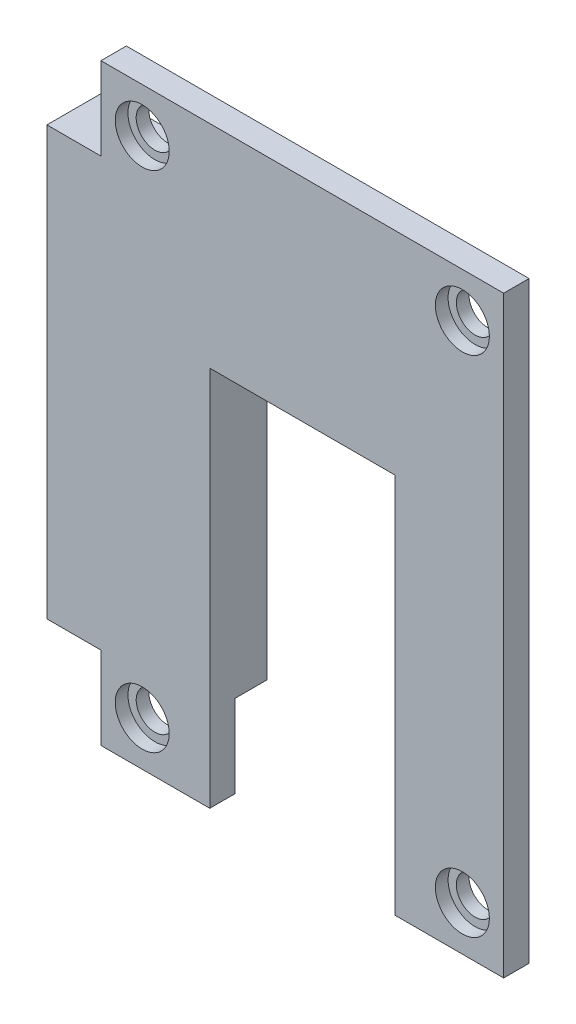
SolidWorks part; units mm, degrees
ref_plane "Alzado" through (0, 0, 0) normal (0, 0, 1) x (1, 0, 0)
ref_plane "Planta" through (0, 0, 0) normal (0, 1, 0) x (1, 0, 0)
ref_plane "Vista lateral" through (0, 0, 0) normal (1, 0, 0) x (0, 0, -1)
sketch "Croquis1" plane through (0, 0, 0) normal (0, 0, 1) x (1, 0, 0)
  line L0 (0, 93.345) -> (64.3868, 93.345)
  line L1 (0, 93.345) -> (0, 0)
  line L2 (0, 0) -> (64.3868, 0)
  line L3 (64.3868, 93.345) -> (64.3868, 0)
  dimension "D1" = 64.3868
  dimension "D2" = 93.345
extrude "Saliente-Extruir1" add sketch "Croquis1" along normal blind 4
sketch "Croquis2" plane through (0, 0, 4) normal (0, 0, 1) x (1, 0, 0)
  line L5 (0, 0) -> (64.3868, 0) construction
  line L6 (18.63, 0) -> (45.7568, 0)
  line L7 (18.63, 0) -> (18.63, 60)
  line L8 (18.63, 60) -> (45.7568, 60)
  line L9 (45.7568, 0) -> (45.7568, 60)
  line L10 (64.3868, 0) -> (64.3868, 93.345) construction
  line L11 (0, 93.345) -> (0, 0) construction
  dimension "D1" = 18.63
  dimension "D2" = 18.63
  dimension "D3" = 60
extrude "Cortar-Extruir1" cut sketch "Croquis2" against normal through all
sketch "Croquis5" plane through (0, 0, 4) normal (0, 0, 1) x (1, 0, 0)
  line L0 (64.3868, 0) -> (64.3868, 93.345) construction
  line L1 (64.3868, 93.345) -> (0, 93.345) construction
  line L2 (0, 93.345) -> (0, 0) construction
  line L3 (45.7568, 0) -> (64.3868, 0) construction
  circle A0 centre (57.3868, 86.345) radius 4.25
  circle A1 centre (7, 86.345) radius 4.25
  circle A2 centre (57.3868, 7) radius 4.25
  circle A3 centre (7, 7) radius 4.25
  dimension "D5" = 8.5
  dimension "D1" = 7
  dimension "D2" = 7
  dimension "D3" = 7
  dimension "D4" = 7
  dimension "D6" = 7
extrude "Cortar-Extruir3" cut sketch "Croquis5" against normal blind 2
sketch "Croquis6" plane through (0, 0, 2) normal (0, 0, 1) x (1, 0, 0)
  circle A0 centre (7, 86.345) radius 2.95
  circle A1 centre (57.3868, 86.345) radius 2.95
  circle A2 centre (57.3868, 7) radius 2.95
  circle A3 centre (7, 7) radius 2.95
  dimension "D1" = 5.9
extrude "Cortar-Extruir4" cut sketch "Croquis6" against normal through all
sketch "Croquis7" plane through (0, 0, 0) normal (0, 0, -1) x (-1, 0, 0)
  line L0 (0, 13) -> (0, 80.345)
  line L3 (0, 13) -> (8, 13)
  line L4 (8, 80.345) -> (8, 13)
  line L5 (0, 93.345) -> (0, 0) construction
  line L6 (0, 80.345) -> (8, 80.345)
  line L7 (-64.3868, 93.345) -> (0, 93.345) construction
  dimension "D1" = 8
  dimension "D2" = 13
  dimension "D3" = 13
extrude "Saliente-Extruir4" add sketch "Croquis7" against normal through all
sketch "Croquis8" plane through (0, 0, 0) normal (0, 0, -1) x (-1, 0, 0)
  line L0 (-18.63, 60) -> (-18.63, 0) construction
  line L1 (8, 80.345) -> (-18.63, 80.345)
  line L2 (8, 80.345) -> (8, 13)
  line L3 (8, 13) -> (-18.63, 13)
  line L4 (-18.63, 80.345) -> (-18.63, 13)
extrude "Saliente-Extruir5" add sketch "Croquis8" along normal blind 5
sketch "Croquis9" plane through (0, 0, 0) normal (0, 0, -1) x (-1, 0, 0)
  line L0 (-64.3868, 93.345) -> (0, 93.345) construction
  line L1 (-63.8868, 93.345) -> (-0.5, 93.345) construction
  line L2 (-63.8868, 93.345) -> (-63.8868, 0)
  line L3 (-63.8868, 0) -> (-0.5, 0) construction
  line L4 (-0.5, 93.345) -> (-0.5, 0) construction
  line L5 (0, 0) -> (-18.63, 0) construction
  line L6 (0, 93.345) -> (0, 80.345) construction
  line L7 (-64.3868, 0) -> (-64.3868, 93.345) construction
  line L8 (-0.5, 93.345) -> (0, 93.345)
  line L9 (0, 93.345) -> (0, 80.345)
  line L10 (0, 80.345) -> (-0.5, 80.345)
  line L11 (-0.5, 0) -> (0, 0)
  line L12 (0, 0) -> (0, 13)
  line L13 (0, 13) -> (-0.5, 13)
  line L14 (-18.63, 13) -> (0, 13) construction
  line L15 (-63.8868, 93.345) -> (-64.3868, 93.345)
  line L16 (-64.3868, 93.345) -> (-64.3868, 0)
  line L17 (-64.3868, 0) -> (-63.8868, 0)
  line L18 (-0.5, 13) -> (-0.5, 0)
  line L19 (-0.5, 80.345) -> (-0.5, 93.345)
  dimension "D1" = 0.5
  dimension "D2" = 0.5
extrude "Cortar-Extruir5" cut sketch "Croquis9" against normal blind 13
sketch "Croquis10" plane through (0, 0, -5) normal (0, 0, -1) x (-1, 0, 0)
  line L0 (8, 13) -> (8, 80.345) construction
  line L1 (8, 56.345) -> (3, 56.345)
  line L2 (8, 56.345) -> (8, 36.345)
  line L3 (8, 36.345) -> (3, 36.345)
  line L4 (3, 56.345) -> (3, 36.345)
  dimension "D1" = 20
  dimension "D2" = 24
  dimension "D3" = 5
extrude "Saliente-Extruir6" add sketch "Croquis10" along normal blind 23
sketch "Croquis11" plane through (0, 0, -28) normal (0, 0, -1) x (-1, 0, 0)
  line L0 (3, 36.345) -> (8, 36.345) construction
  line L1 (8, 56.345) -> (-12, 56.345)
  line L2 (8, 56.345) -> (8, 36.345)
  line L3 (8, 36.345) -> (-12, 36.345)
  line L4 (-12, 56.345) -> (-12, 36.345)
  dimension "D1" = 20
extrude "Saliente-Extruir7" add sketch "Croquis11" along normal blind 5
sketch "Croquis12" plane through (0, 0, -5) normal (0, 0, -1) x (-1, 0, 0)
  line L0 (-45.7568, 0) -> (-63.8868, 0) construction
  line L1 (-17.63, 60) -> (-46.7568, 60)
  line L2 (-17.63, 60) -> (-17.63, 0)
  line L3 (-17.63, 0) -> (-46.7568, 0)
  line L4 (-46.7568, 60) -> (-46.7568, 0)
  line L5 (-45.7568, 0) -> (-45.7568, 60) construction
  line L6 (-18.63, 80.345) -> (-18.63, 13) construction
  line L7 (-45.7568, 60) -> (-18.63, 60) construction
  dimension "D1" = 1
  dimension "D2" = 1
extrude "Cortar-Extruir6" cut sketch "Croquis12" against normal through all
sketch "Croquis13" plane through (0, 0, -5) normal (0, 0, -1) x (-1, 0, 0)
  line L1 (-18.63, 80.345) -> (-17.63, 80.345)
  line L2 (-18.63, 80.345) -> (-18.63, 60)
  line L3 (-18.63, 60) -> (-17.63, 60)
  line L4 (-17.63, 80.345) -> (-17.63, 60)
extrude "Cortar-Extruir7" cut sketch "Croquis13" against normal blind 5
sketch "Croquis14" plane through (-8, 0, 0) normal (-1, 0, 0) x (0, 0, 1)
  line L0 (-33, 36.345) -> (-5, 36.345) construction
  line L1 (-5, 56.345) -> (-27, 56.345) construction
  line L2 (-5, 56.345) -> (-5, 36.345) construction
  line L3 (-5, 36.345) -> (-27, 36.345) construction
  line L4 (-27, 56.345) -> (-27, 36.345) construction
  line L5 (-33, 36.345) -> (-33, 56.345) construction
  circle A0 centre (-7.25, 46.345) radius 1.5
  circle A1 centre (-24.75, 46.345) radius 1.5
  point P11 (0, 0)
  point P12 (-33, 46.345)
  point P13 (0, 0)
  dimension "D1" = 3
  dimension "D2" = 3
  dimension "D3" = 17.5
  dimension "D4" = 22
  dimension "D5" = 2.25
extrude "Cortar-Extruir8" cut sketch "Croquis14" against normal blind 5
